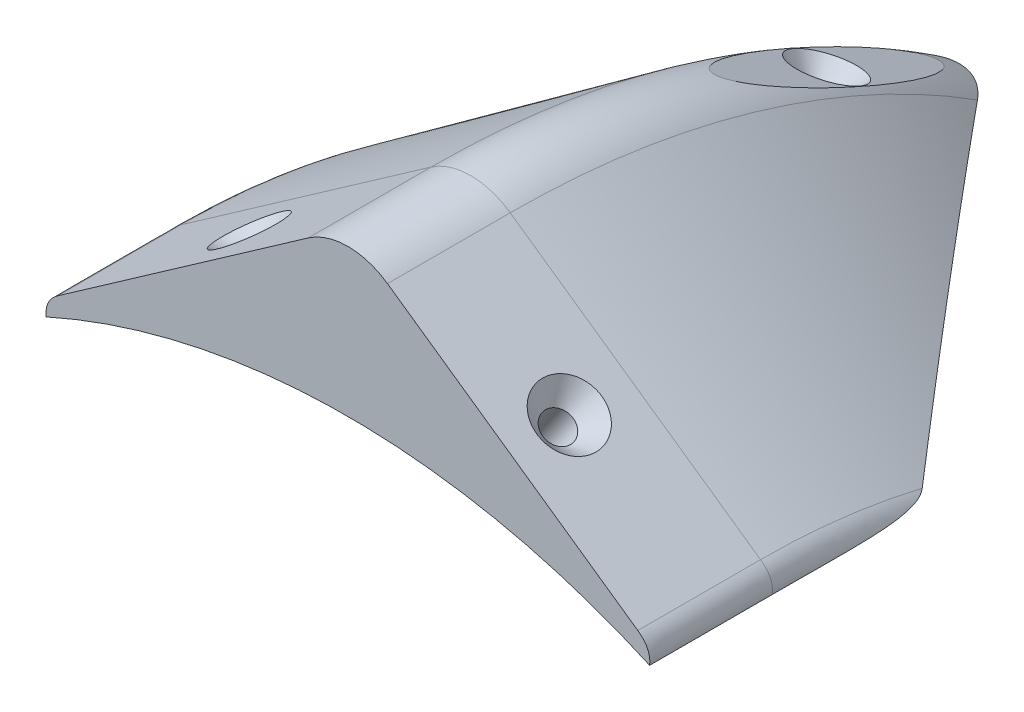
SolidWorks part; units mm, degrees
ref_plane "Front Plane" through (0, 0, 0) normal (0, 0, 1) x (1, 0, 0)
ref_plane "Top Plane" through (0, 0, 0) normal (0, 1, 0) x (1, 0, 0)
ref_plane "Right Plane" through (0, 0, 0) normal (1, 0, 0) x (0, 0, -1)
sketch "Sketch1" plane through (0, 0, 0) normal (0, 0, 1) x (1, 0, 0)
  line L0 (0, 0) -> (0, 152.4) construction
  line L1 (-59.9912, 144.0357) -> (-8.1938, 180.2969)
  line L7 (0, 0) -> (74.48, 0) construction
  line L20 (59.9912, 144.0357) -> (8.1938, 180.2969)
  arc A1 (8.1938, 180.2969) -> (-8.1938, 180.2969) centre (0, 168.5925) ccw
  arc A7 (62.4412, 139.0211) -> (-62.4412, 139.0211) centre (0, 0) ccw
  spline S2 degree 2 poles (-59.9912, 144.0357) (-62.7825, 142.084) (-62.4412, 139.0211) knots 0 0 0 1 1 1
  spline S3 degree 2 poles (59.9912, 144.0357) (62.7825, 142.084) (62.4412, 139.0211) knots 0 0 0 1 1 1
  dimension "D2" = 63.2286
  dimension "D3" = 28.575
  dimension "D12" = 5.8922
  dimension "D5" = 152.4
  dimension "D1" = 168.5925
  dimension "D4" = 51.7974
  dimension "D14" = 1.791
  dimension "D15" = 3.2237
revolve "Revolve1" add sketch "Sketch1" angle 57 about L7 reverse direction yes
sketch "Sketch3" plane through (0, 0, 0) normal (0, 0, 1) x (1, 0, 0)
  line L0 (0, 0) -> (0, 152.4) construction
  line L2 (-59.9912, 144.0357) -> (-8.1938, 180.2969)
  line L4 (19.2885, 0) -> (93.7685, 0) construction
  line L5 (59.9912, 144.0357) -> (8.1938, 180.2969)
  arc A2 (8.1938, 180.2969) -> (-8.1938, 180.2969) centre (0, 168.5925) ccw
  arc A3 (62.4412, 139.0211) -> (-62.4412, 139.0211) centre (0, 0) ccw
  spline S0 degree 2 poles (-59.9912, 144.0357) (-62.7825, 142.084) (-62.4412, 139.0211) knots 0 0 0 1 1 1
  spline S1 degree 2 poles (59.9912, 144.0357) (62.7825, 142.084) (62.4412, 139.0211) knots 0 0 0 1 1 1
  dimension "D2" = 28.575
  dimension "D3" = 5.8922
  dimension "D8" = 152.4
  dimension "D1" = 168.5925
  dimension "D4" = 1.791
  dimension "D5" = 3.2237
  dimension "D6" = 63.2286
  dimension "D7" = 51.7974
extrude "Boss-Extrude1" add sketch "Sketch3" along normal blind 25.4
ref_plane "Plane1" through (0, 0, 12.7) normal (0, 0, 1) x (1, 0, 0)
sketch "Sketch7" plane through (0, 0, 12.7) normal (0, 0, 1) x (1, 0, 0)
  line L0 (-30.5085, 164.6753) -> (-18.8551, 148.029) construction
  line L1 (-8.1938, 180.2969) -> (-59.9912, 144.0357) construction
  line L2 (-18.8551, 148.029) -> (-21.4561, 146.2082)
  line L3 (-21.4561, 146.2082) -> (-37.8066, 169.5641) construction
  line L4 (-30.7642, 159.5044) -> (-19.1086, 167.6641) construction
  line L5 (-21.4561, 146.2082) -> (-33.1095, 162.8545)
  line L6 (-18.8551, 148.029) -> (-28.1633, 161.3253)
  line L7 (-33.1095, 162.8545) -> (-27.585, 166.722)
  line L8 (-27.585, 166.722) -> (-28.1633, 161.3253)
  line L9 (0, 0) -> (0, 246.8513) construction
  circle A0 centre (0, 0) radius 152.4 construction
  circle A1 centre (0, 0) radius 149.225 construction
  dimension "D1" = 16.2306
  dimension "D2" = 3.175
  dimension "D3" = 4.0894
  dimension "D4" = 6.7437
revolve "Cut-Revolve2" cut sketch "Sketch7" angle 360 about L3
mirror "Mirror2" about plane through (0, 0, 0) normal (1, 0, 0) of "Cut-Revolve2"
sketch "Sketch8" plane through (0, 0, 25.4) normal (0, 0, 1) x (1, 0, 0)
  circle A0 centre (0, 0) radius 152.4
extrude "Cut-Extrude3" cut sketch "Sketch8" against normal blind 257.048
sketch "Sketch10" plane through (0, 0, 0) normal (1, 0, 0) x (0, 0, -1)
  line L0 (0, 0) -> (74.384, 167.0692)
  line L1 (0, 0) -> (0, 180.2969) construction
  line L2 (0, 0) -> (50.4086, 175.7955)
  line L3 (50.4086, 175.7955) -> (74.384, 167.0692)
  arc A1 (101.0907, 152.4) -> (0, 182.88) centre (0, 0) ccw construction
  dimension "D1" = 24
  dimension "D2" = 16
  dimension "D3" = 25.5141
ref_plane "Plane2" through (0, 167.0692, -74.384) normal (0, 0.9135, -0.4067) x (1, 0, 0)
sketch "Sketch13" plane through (0, 167.0692, -74.384) normal (0, 0.9135, -0.4067) x (1, 0, 0)
  line L0 (8.1938, 26.4309) -> (8.1938, -73.3334) construction
  line L1 (8.1938, 63.5) -> (-8.1938, 63.5)
  line L2 (8.1938, 63.5) -> (8.1938, -63.5)
  line L3 (8.1938, -63.5) -> (-8.1938, -63.5)
  line L4 (-8.1938, 63.5) -> (-8.1938, -63.5)
  line L5 (-8.1938, 26.4309) -> (-8.1938, -73.3334) construction
  dimension "D1" = 127
  dimension "D2" = 63.5
extrude "Cut-Extrude5" cut sketch "Sketch13" against normal blind 1.778
sketch "Sketch14" plane through (0, 0, 0) normal (1, 0, 0) x (0, 0, -1)
  line L0 (73.6608, 165.4449) -> (67.5001, 168.1878)
  line L1 (96.9008, 155.0978) -> (50.4208, 175.792) construction
  line L2 (73.6608, 165.4449) -> (63.3297, 142.2409)
  line L3 (0, 0) -> (74.384, 167.0692) construction
  line L4 (63.3297, 142.2409) -> (60.4292, 143.5322)
  line L5 (60.4292, 143.5322) -> (69.097, 163.0004)
  line L6 (67.5001, 168.1878) -> (69.097, 163.0004)
  dimension "D1" = 6.7437
  dimension "D2" = 25.4
  dimension "D3" = 3.175
  dimension "D4" = 21.3106
revolve "Cut-Revolve4" cut sketch "Sketch14" angle 360 about L2
